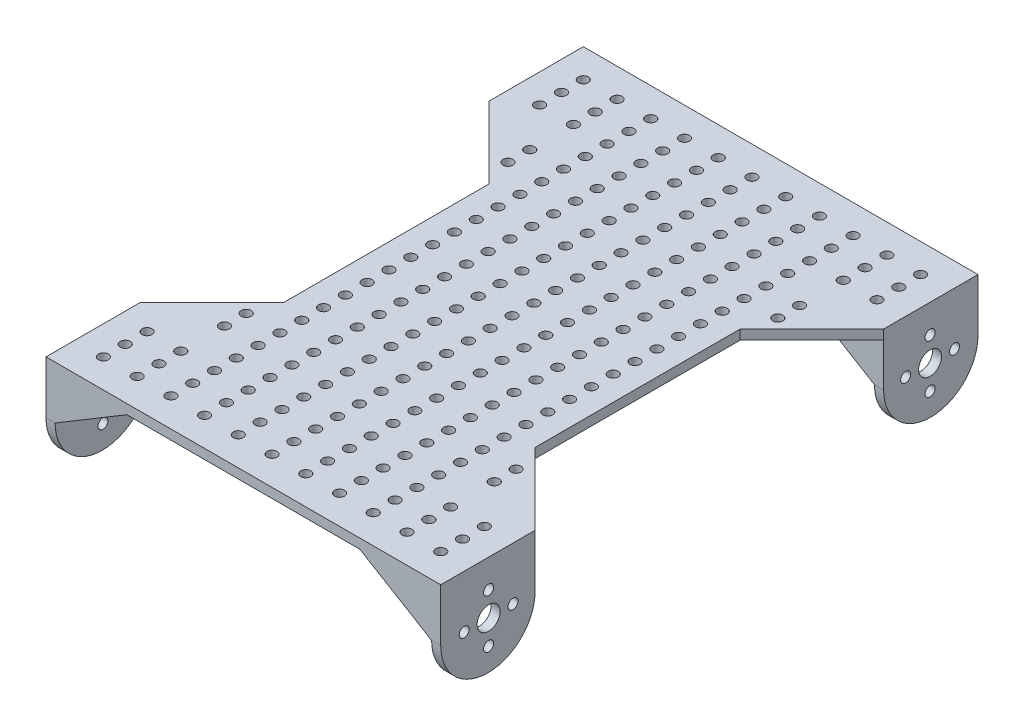
SolidWorks part; units mm, degrees
ref_plane "Alzado" through (0, 0, 0) normal (0, 0, 1) x (1, 0, 0)
ref_plane "Planta" through (0, 0, 0) normal (0, 1, 0) x (1, 0, 0)
ref_plane "Vista lateral" through (0, 0, 0) normal (1, 0, 0) x (0, 0, -1)
sketch "Croquis1" plane through (0, 0, 0) normal (1, 0, 0) x (0, 0, -1)
  point P0 (0, 0)
  line B0 (-60.7, 0) -> (60.7, 0)
  line B1 (-93.6, 0) -> (-93.6, 3.3682)
  line B2 (-93.6, 3.3682) -> (93.6, 3.3682)
  line B3 (-93.6, 0) -> (-93.6, -15)
  line B4 (-60.7, -15) -> (-63.7, -15) construction
  line B5 (-93.6, 0) -> (-60.7, 0) construction
  line B6 (-60.7, -15) -> (-60.7, 0)
  line B7 (0, 3.3682) -> (0, 0) construction
  line B8 (93.6, 0) -> (60.7, 0) construction
  line B9 (60.7, -15) -> (63.7, -15) construction
  line B10 (60.7, -15) -> (60.7, 0)
  line B11 (93.6, 0) -> (93.6, -15)
  line B12 (93.6, 0) -> (93.6, 3.3682)
  line B13 (93.6, 0) -> (60.7, 0) construction
  arc B14 (-93.6, -15) -> (-60.7, -15) centre (-77.15, -15) ccw
  circle B15 centre (-76.9, -15) radius 13.2
  circle B16 centre (76.9, -15) radius 13.2
  arc B17 (93.6, -15) -> (60.7, -15) centre (77.15, -15) cw
  circle B18 centre (-76.9, -23.5) radius 1.75
  circle B19 centre (-85.4, -15) radius 1.75
  circle B20 centre (-68.4, -15) radius 1.75
  circle B21 centre (-76.9, -6.5) radius 1.75
  circle B22 centre (76.9, -6.5) radius 1.75
  circle B23 centre (68.4, -15) radius 1.75
  circle B24 centre (85.4, -15) radius 1.75
  circle B25 centre (76.9, -23.5) radius 1.75
  circle B26 centre (-76.9, -15) radius 4
  circle B27 centre (76.9, -15) radius 4
sketch_block_instance "Bloque1-1"
sketch_block "Bloque1"
extrude "Saliente-Extruir1" add sketch "Croquis1" along normal blind 3.175 contours B17 B11 B12 B2 B1 B3 B14 B6 B0 B10 B15 B16 | B15 B26 B21 B20 B19 B18 | B16 B25 B23 B22 B24 B27 region at (0, -7.5, 62.6041) region at (0, -15, 89.7266) region at (0, -15, -64.0734)
sketch "Croquis3" plane through (3.175, 0, 0) normal (1, 0, 0) x (0, 0, -1)
  line L0 (-93.6, 3.3682) -> (-93.6, 0)
  line L1 (-93.6, -15) -> (-93.6, 3.3682) construction
  line L2 (-93.6, 0) -> (93.6, 0)
  line L3 (93.6, 3.3682) -> (93.6, -15) construction
  line L4 (93.6, 0) -> (93.6, 3.3682)
  line L5 (93.6, 3.3682) -> (-93.6, 3.3682)
extrude "Saliente-Extruir2" add sketch "Croquis3" along normal blind 131.175 and the other way blind 3.175
sketch "Croquis4" plane through (134.35, 0, 0) normal (1, 0, 0) x (0, 0, -1)
  line L0 (93.6, 0) -> (60.7, 0) construction
  line L1 (60.7, 0) -> (60.7, -15) construction
  line L2 (93.6, -15) -> (93.6, 0) construction
  line L3 (-60.7, 0) -> (-93.6, 0) construction
  line L4 (93.6, 3.3682) -> (-93.6, 3.3682)
  line L5 (-93.6, 3.3682) -> (-93.6, 0)
  line L6 (-93.6, 0) -> (93.6, 0)
  line L7 (93.6, 0) -> (93.6, 3.3682)
  line L8 (93.6, 3.3682) -> (-93.6, 3.3682)
  line L9 (-93.6, 3.3682) -> (-93.6, 0)
  line L10 (-93.6, 0) -> (93.6, 0)
  line L11 (93.6, 0) -> (93.6, 3.3682)
  line L12 (-93.6, 0) -> (-93.6, -15) construction
  line L13 (-60.7, -15) -> (-60.7, 0) construction
  line L14 (93.6, 0) -> (60.7, 0)
  line L15 (60.7, 0) -> (60.7, -15)
  line L16 (93.6, -15) -> (93.6, 0)
  line L17 (-60.7, 0) -> (-93.6, 0)
  line L18 (-93.6, 0) -> (-93.6, -15)
  line L19 (-60.7, -15) -> (-60.7, 0)
  arc A0 (60.7, -15) -> (93.6, -15) centre (77.15, -15) ccw construction
  circle A1 centre (76.9, -15) radius 4
  circle A2 centre (76.9, -15) radius 4
  circle A3 centre (85.4, -15) radius 1.75
  circle A4 centre (85.4, -15) radius 1.75
  circle A5 centre (76.9, -6.5) radius 1.75
  circle A6 centre (76.9, -6.5) radius 1.75
  circle A7 centre (68.4, -15) radius 1.75
  circle A8 centre (68.4, -15) radius 1.75
  circle A9 centre (76.9, -23.5) radius 1.75
  circle A10 centre (76.9, -23.5) radius 1.75
  circle A11 centre (-76.9, -15) radius 4
  circle A12 centre (-76.9, -15) radius 4
  circle A13 centre (-76.9, -6.5) radius 1.75
  circle A14 centre (-76.9, -6.5) radius 1.75
  circle A15 centre (-68.4, -15) radius 1.75
  circle A16 centre (-68.4, -15) radius 1.75
  circle A17 centre (-85.4, -15) radius 1.75
  circle A18 centre (-85.4, -15) radius 1.75
  circle A19 centre (-76.9, -23.5) radius 1.75
  circle A20 centre (-76.9, -23.5) radius 1.75
  arc A21 (-93.6, -15) -> (-60.7, -15) centre (-77.15, -15) ccw construction
  arc A22 (60.7, -15) -> (93.6, -15) centre (77.15, -15) ccw
  arc A23 (-93.6, -15) -> (-60.7, -15) centre (-77.15, -15) ccw
  line M16 (93.6, 3.3682) -> (-93.6, 3.3682)
  line M17 (-93.6, 3.3682) -> (-93.6, 0)
  line M18 (-93.6, 0) -> (93.6, 0)
  line M19 (93.6, 0) -> (93.6, 3.3682)
  dimension "D1" = 0
  dimension "D2" = 0
  dimension "D3" = 0
  dimension "D4" = 0
  dimension "D5" = 0
  dimension "D6" = 0
  dimension "D7" = 0
  dimension "D8" = 0
  dimension "D9" = 0
  dimension "D10" = 0
  dimension "D11" = 0
extrude "Saliente-Extruir3" add sketch "Croquis4" along normal blind 3.175 contours L18 A23 L19 A12 A14 A16 A18 A20 M18 | L10 M19 M16 M17 M18 | L15 A22 L16 L10 A2 A4 A6 A8 A10 region at (134.35, 1.6841, 0) region at (134.35, -7.5, -93.1449) region at (134.35, -0.4551, 77.15)
sketch "Croquis5" plane through (0, 3.3682, 0) normal (0, 1, 0) x (1, 0, 0)
  line L0 (0, 60.7) -> (25, 35.7)
  line L1 (0, -93.6) -> (0, 93.6) construction
  line L2 (25, 35.7) -> (25, -35.7)
  line L3 (25, -35.7) -> (0, -60.7)
  line L4 (0, -60.7) -> (0, 60.7)
  line L5 (68.7625, 93.6) -> (68.7625, -93.6) construction
  line L6 (137.525, 93.6) -> (0, 93.6) construction
  line L7 (137.525, -93.6) -> (0, -93.6) construction
  line L8 (137.525, 60.7) -> (112.525, 35.7)
  line L9 (137.525, -60.7) -> (137.525, 60.7)
  line L10 (112.525, -35.7) -> (137.525, -60.7)
  line L11 (112.525, 35.7) -> (112.525, -35.7)
  point P12 (27.0441, -39.4213)
  point P15 (-120.5667, 86.0572)
  dimension "D1" = 32.9
  dimension "D2" = 32.9
  dimension "D3" = 25
  dimension "D4" = 25
  dimension "D5" = 25
extrude "Cortar-Extruir1" cut sketch "Croquis5" against normal through all
sketch "Croquis8" plane through (0, 0, 93.6) normal (0, 0, 1) x (1, 0, 0)
  line L0 (3.175, -15) -> (28.175, 0)
  line L1 (3.175, 0) -> (134.35, 0) construction
  line L2 (28.175, 0) -> (3.175, 0)
  line L3 (3.175, 0) -> (3.175, -15)
  line L4 (68.7625, 0) -> (68.7625, 3.3682) construction
  line L5 (137.525, 3.3682) -> (0, 3.3682) construction
  line L6 (134.35, 0) -> (134.35, -15)
  line L7 (109.35, 0) -> (134.35, 0)
  line L8 (134.35, -15) -> (109.35, 0)
  dimension "D1" = 25
extrude "Saliente-Extruir4" add sketch "Croquis8" against normal up to surface (187.2 mm away) up to face at (68.7625, -6.658, -93.6)
ref_plane "Plano1" through (68.7625, 0, 0) normal (1, 0, 0) x (0, 0, -1)
sketch "Croquis9" plane through (68.7625, 0, 0) normal (1, 0, 0) x (0, 0, -1)
  line L0 (-63.7, -15) -> (-63.7, 0)
  line L1 (-72.9, -15) -> (-80.9, -15) construction
  line L2 (-63.7, 0) -> (-90.6, 0)
  line L3 (-90.6, 0) -> (-90.6, -15)
  line L4 (-90.6, -15) -> (-63.7, -15)
  line L5 (-93.6, 3.3682) -> (-93.6, -15) construction
  line L6 (-60.7, -15) -> (-60.7, 0) construction
  line L7 (57.525, 0) -> (-57.525, 0) construction
  line L8 (60.7, 0) -> (-60.7, 0)
  line L9 (0, 0) -> (0, -15)
  line L10 (60.7, -15) -> (-60.7, -15)
  line L11 (-60.7, 0) -> (-60.7, -15)
  line L12 (90.6, -15) -> (63.7, -15)
  line L13 (90.6, 0) -> (90.6, -15)
  line L14 (63.7, 0) -> (90.6, 0)
  line L15 (63.7, -15) -> (63.7, 0)
  line L16 (60.7, 0) -> (60.7, -15)
  dimension "D1" = 3
  dimension "D2" = 3
extrude "Cortar-Extruir2" cut sketch "Croquis9" along normal up to surface (65.5875 mm away) and the other way up to surface (65.5875 mm away) contours L16 L10 L11 L8 | L13 L12 L15 L14 | L4 L0 L2 L3 up to face at (134.35, -23.5, -78.65) other way up to face at (3.175, -17.9938, -76.9625)
sketch "Croquis10" plane through (0, 3.3682, 0) normal (0, 1, 0) x (1, 0, 0)
  line L0 (0, 60.7) -> (0, 93.6) construction
  line L1 (137.525, 93.6) -> (0, 93.6) construction
  line L2 (137.525, 93.6) -> (137.525, 60.7) construction
  line L3 (10, 83.6) -> (127.525, 83.6) construction
  line L4 (0, -93.6) -> (0, -60.7) construction
  line L5 (137.525, -93.6) -> (0, -93.6) construction
  line L6 (10, 76) -> (127.525, 76) construction
  line L7 (10, 68.4) -> (127.525, 68.4) construction
  line L8 (10, 60.8) -> (127.525, 60.8) construction
  line L9 (10, 53.2) -> (127.525, 53.2) construction
  line L10 (10, 45.6) -> (127.525, 45.6) construction
  line L11 (10, 38) -> (127.525, 38) construction
  line L12 (10, 30.4) -> (127.525, 30.4) construction
  line L13 (10, 22.8) -> (127.525, 22.8) construction
  line L14 (10, 15.2) -> (127.525, 15.2) construction
  line L15 (10, 7.6) -> (127.525, 7.6) construction
  line L16 (10, 0) -> (127.525, 0) construction
  line L17 (10, -7.6) -> (127.525, -7.6) construction
  line L18 (10, -15.2) -> (127.525, -15.2) construction
  line L19 (10, -22.8) -> (127.525, -22.8) construction
  line L20 (10, -30.4) -> (127.525, -30.4) construction
  line L21 (10, -38) -> (127.525, -38) construction
  line L22 (10, -45.6) -> (127.525, -45.6) construction
  line L23 (10, -53.2) -> (127.525, -53.2) construction
  line L24 (10, -60.8) -> (127.525, -60.8) construction
  line L25 (10, -68.4) -> (127.525, -68.4) construction
  line L26 (10, -76) -> (127.525, -76) construction
  line L27 (10, -83.6) -> (127.525, -83.6) construction
  circle A0 centre (10, 83.6) radius 1.75
  circle A1 centre (127.525, 83.6) radius 1.75
  circle A5 centre (21.753, 83.6) radius 1.75
  circle A6 centre (33.506, 83.6) radius 1.75
  circle A7 centre (45.259, 83.6) radius 1.75
  circle A8 centre (57.012, 83.6) radius 1.75
  circle A9 centre (68.765, 83.6) radius 1.75
  circle A10 centre (80.518, 83.6) radius 1.75
  circle A11 centre (92.271, 83.6) radius 1.75
  circle A12 centre (104.024, 83.6) radius 1.75
  circle A13 centre (115.777, 83.6) radius 1.75
  circle A14 centre (127.53, 83.6) radius 1.75
  circle A15 centre (10, -83.6) radius 1.75
  circle A16 centre (10, 76) radius 1.75
  circle A17 centre (127.525, 76) radius 1.75
  circle A18 centre (21.753, 76) radius 1.75
  circle A19 centre (33.506, 76) radius 1.75
  circle A20 centre (45.259, 76) radius 1.75
  circle A21 centre (57.012, 76) radius 1.75
  circle A22 centre (68.765, 76) radius 1.75
  circle A23 centre (80.518, 76) radius 1.75
  circle A24 centre (92.271, 76) radius 1.75
  circle A25 centre (104.024, 76) radius 1.75
  circle A26 centre (115.777, 76) radius 1.75
  circle A27 centre (127.53, 76) radius 1.75
  circle A28 centre (10, 68.4) radius 1.75
  circle A29 centre (127.525, 68.4) radius 1.75
  circle A30 centre (21.753, 68.4) radius 1.75
  circle A31 centre (33.506, 68.4) radius 1.75
  circle A32 centre (45.259, 68.4) radius 1.75
  circle A33 centre (57.012, 68.4) radius 1.75
  circle A34 centre (68.765, 68.4) radius 1.75
  circle A35 centre (80.518, 68.4) radius 1.75
  circle A36 centre (92.271, 68.4) radius 1.75
  circle A37 centre (104.024, 68.4) radius 1.75
  circle A38 centre (115.777, 68.4) radius 1.75
  circle A39 centre (127.53, 68.4) radius 1.75
  circle A40 centre (10, 60.8) radius 1.75 construction
  circle A41 centre (127.525, 60.8) radius 1.75 construction
  circle A42 centre (21.753, 60.8) radius 1.75 construction
  circle A43 centre (33.506, 60.8) radius 1.75
  circle A44 centre (45.259, 60.8) radius 1.75
  circle A45 centre (57.012, 60.8) radius 1.75
  circle A46 centre (68.765, 60.8) radius 1.75
  circle A47 centre (80.518, 60.8) radius 1.75
  circle A48 centre (92.271, 60.8) radius 1.75
  circle A49 centre (104.024, 60.8) radius 1.75
  circle A50 centre (115.777, 60.8) radius 1.75 construction
  circle A51 centre (127.53, 60.8) radius 1.75 construction
  circle A52 centre (10, 53.2) radius 1.75 construction
  circle A53 centre (127.525, 53.2) radius 1.75 construction
  circle A54 centre (21.753, 53.2) radius 1.75
  circle A55 centre (33.506, 53.2) radius 1.75
  circle A56 centre (45.259, 53.2) radius 1.75
  circle A57 centre (57.012, 53.2) radius 1.75
  circle A58 centre (68.765, 53.2) radius 1.75
  circle A59 centre (80.518, 53.2) radius 1.75
  circle A60 centre (92.271, 53.2) radius 1.75
  circle A61 centre (104.024, 53.2) radius 1.75
  circle A62 centre (115.777, 53.2) radius 1.75
  circle A63 centre (127.53, 53.2) radius 1.75 construction
  circle A64 centre (10, 45.6) radius 1.75
  circle A65 centre (127.525, 45.6) radius 1.75
  circle A66 centre (21.753, 45.6) radius 1.75
  circle A67 centre (33.506, 45.6) radius 1.75
  circle A68 centre (45.259, 45.6) radius 1.75
  circle A69 centre (57.012, 45.6) radius 1.75
  circle A70 centre (68.765, 45.6) radius 1.75
  circle A71 centre (80.518, 45.6) radius 1.75
  circle A72 centre (92.271, 45.6) radius 1.75
  circle A73 centre (104.024, 45.6) radius 1.75
  circle A74 centre (115.777, 45.6) radius 1.75
  circle A75 centre (127.53, 45.6) radius 1.75
  circle A76 centre (10, 38) radius 1.75
  circle A77 centre (127.525, 38) radius 1.75
  circle A78 centre (21.753, 38) radius 1.75 construction
  circle A79 centre (33.506, 38) radius 1.75
  circle A80 centre (45.259, 38) radius 1.75
  circle A81 centre (57.012, 38) radius 1.75
  circle A82 centre (68.765, 38) radius 1.75
  circle A83 centre (80.518, 38) radius 1.75
  circle A84 centre (92.271, 38) radius 1.75
  circle A85 centre (104.024, 38) radius 1.75
  circle A86 centre (115.777, 38) radius 1.75 construction
  circle A87 centre (127.53, 38) radius 1.75
  circle A88 centre (10, 30.4) radius 1.75
  circle A89 centre (127.525, 30.4) radius 1.75
  circle A90 centre (21.753, 30.4) radius 1.75
  circle A91 centre (33.506, 30.4) radius 1.75
  circle A92 centre (45.259, 30.4) radius 1.75
  circle A93 centre (57.012, 30.4) radius 1.75
  circle A94 centre (68.765, 30.4) radius 1.75
  circle A95 centre (80.518, 30.4) radius 1.75
  circle A96 centre (92.271, 30.4) radius 1.75
  circle A97 centre (104.024, 30.4) radius 1.75
  circle A98 centre (115.777, 30.4) radius 1.75
  circle A99 centre (127.53, 30.4) radius 1.75
  circle A100 centre (10, 22.8) radius 1.75
  circle A101 centre (127.525, 22.8) radius 1.75
  circle A102 centre (21.753, 22.8) radius 1.75
  circle A103 centre (33.506, 22.8) radius 1.75
  circle A104 centre (45.259, 22.8) radius 1.75
  circle A105 centre (57.012, 22.8) radius 1.75
  circle A106 centre (68.765, 22.8) radius 1.75
  circle A107 centre (80.518, 22.8) radius 1.75
  circle A108 centre (92.271, 22.8) radius 1.75
  circle A109 centre (104.024, 22.8) radius 1.75
  circle A110 centre (115.777, 22.8) radius 1.75
  circle A111 centre (127.53, 22.8) radius 1.75
  circle A112 centre (10, 15.2) radius 1.75
  circle A113 centre (127.525, 15.2) radius 1.75
  circle A114 centre (21.753, 15.2) radius 1.75
  circle A115 centre (33.506, 15.2) radius 1.75
  circle A116 centre (45.259, 15.2) radius 1.75
  circle A117 centre (57.012, 15.2) radius 1.75
  circle A118 centre (68.765, 15.2) radius 1.75
  circle A119 centre (80.518, 15.2) radius 1.75
  circle A120 centre (92.271, 15.2) radius 1.75
  circle A121 centre (104.024, 15.2) radius 1.75
  circle A122 centre (115.777, 15.2) radius 1.75
  circle A123 centre (127.53, 15.2) radius 1.75
  circle A124 centre (10, 7.6) radius 1.75
  circle A125 centre (127.525, 7.6) radius 1.75
  circle A126 centre (21.753, 7.6) radius 1.75
  circle A127 centre (33.506, 7.6) radius 1.75
  circle A128 centre (45.259, 7.6) radius 1.75
  circle A129 centre (57.012, 7.6) radius 1.75
  circle A130 centre (68.765, 7.6) radius 1.75
  circle A131 centre (80.518, 7.6) radius 1.75
  circle A132 centre (92.271, 7.6) radius 1.75
  circle A133 centre (104.024, 7.6) radius 1.75
  circle A134 centre (115.777, 7.6) radius 1.75
  circle A135 centre (127.53, 7.6) radius 1.75
  circle A136 centre (10, 0) radius 1.75
  circle A137 centre (127.525, 0) radius 1.75
  circle A138 centre (21.753, 0) radius 1.75
  circle A139 centre (33.506, 0) radius 1.75
  circle A140 centre (45.259, 0) radius 1.75
  circle A141 centre (57.012, 0) radius 1.75
  circle A142 centre (68.765, 0) radius 1.75
  circle A143 centre (80.518, 0) radius 1.75
  circle A144 centre (92.271, 0) radius 1.75
  circle A145 centre (104.024, 0) radius 1.75
  circle A146 centre (115.777, 0) radius 1.75
  circle A147 centre (127.53, 0) radius 1.75
  circle A148 centre (10, -7.6) radius 1.75
  circle A149 centre (127.525, -7.6) radius 1.75
  circle A150 centre (21.753, -7.6) radius 1.75
  circle A151 centre (33.506, -7.6) radius 1.75
  circle A152 centre (45.259, -7.6) radius 1.75
  circle A153 centre (57.012, -7.6) radius 1.75
  circle A154 centre (68.765, -7.6) radius 1.75
  circle A155 centre (80.518, -7.6) radius 1.75
  circle A156 centre (92.271, -7.6) radius 1.75
  circle A157 centre (104.024, -7.6) radius 1.75
  circle A158 centre (115.777, -7.6) radius 1.75
  circle A159 centre (127.53, -7.6) radius 1.75
  circle A160 centre (10, -15.2) radius 1.75
  circle A161 centre (127.525, -15.2) radius 1.75
  circle A162 centre (21.753, -15.2) radius 1.75
  circle A163 centre (33.506, -15.2) radius 1.75
  circle A164 centre (45.259, -15.2) radius 1.75
  circle A165 centre (57.012, -15.2) radius 1.75
  circle A166 centre (68.765, -15.2) radius 1.75
  circle A167 centre (80.518, -15.2) radius 1.75
  circle A168 centre (92.271, -15.2) radius 1.75
  circle A169 centre (104.024, -15.2) radius 1.75
  circle A170 centre (115.777, -15.2) radius 1.75
  circle A171 centre (127.53, -15.2) radius 1.75
  circle A172 centre (10, -22.8) radius 1.75
  circle A173 centre (127.525, -22.8) radius 1.75
  circle A174 centre (21.753, -22.8) radius 1.75
  circle A175 centre (33.506, -22.8) radius 1.75
  circle A176 centre (45.259, -22.8) radius 1.75
  circle A177 centre (57.012, -22.8) radius 1.75
  circle A178 centre (68.765, -22.8) radius 1.75
  circle A179 centre (80.518, -22.8) radius 1.75
  circle A180 centre (92.271, -22.8) radius 1.75
  circle A181 centre (104.024, -22.8) radius 1.75
  circle A182 centre (115.777, -22.8) radius 1.75
  circle A183 centre (127.53, -22.8) radius 1.75
  circle A184 centre (10, -30.4) radius 1.75
  circle A185 centre (127.525, -30.4) radius 1.75
  circle A186 centre (21.753, -30.4) radius 1.75
  circle A187 centre (33.506, -30.4) radius 1.75
  circle A188 centre (45.259, -30.4) radius 1.75
  circle A189 centre (57.012, -30.4) radius 1.75
  circle A190 centre (68.765, -30.4) radius 1.75
  circle A191 centre (80.518, -30.4) radius 1.75
  circle A192 centre (92.271, -30.4) radius 1.75
  circle A193 centre (104.024, -30.4) radius 1.75
  circle A194 centre (115.777, -30.4) radius 1.75
  circle A195 centre (127.53, -30.4) radius 1.75
  circle A196 centre (10, -38) radius 1.75
  circle A197 centre (127.525, -38) radius 1.75
  circle A198 centre (21.753, -38) radius 1.75 construction
  circle A199 centre (33.506, -38) radius 1.75
  circle A200 centre (45.259, -38) radius 1.75
  circle A201 centre (57.012, -38) radius 1.75
  circle A202 centre (68.765, -38) radius 1.75
  circle A203 centre (80.518, -38) radius 1.75
  circle A204 centre (92.271, -38) radius 1.75
  circle A205 centre (104.024, -38) radius 1.75
  circle A206 centre (115.777, -38) radius 1.75 construction
  circle A207 centre (127.53, -38) radius 1.75
  circle A208 centre (10, -45.6) radius 1.75
  circle A209 centre (127.525, -45.6) radius 1.75
  circle A210 centre (21.753, -45.6) radius 1.75
  circle A211 centre (33.506, -45.6) radius 1.75
  circle A212 centre (45.259, -45.6) radius 1.75
  circle A213 centre (57.012, -45.6) radius 1.75
  circle A214 centre (68.765, -45.6) radius 1.75
  circle A215 centre (80.518, -45.6) radius 1.75
  circle A216 centre (92.271, -45.6) radius 1.75
  circle A217 centre (104.024, -45.6) radius 1.75
  circle A218 centre (115.777, -45.6) radius 1.75
  circle A219 centre (127.53, -45.6) radius 1.75
  circle A220 centre (10, -53.2) radius 1.75 construction
  circle A221 centre (127.525, -53.2) radius 1.75 construction
  circle A222 centre (21.753, -53.2) radius 1.75
  circle A223 centre (33.506, -53.2) radius 1.75
  circle A224 centre (45.259, -53.2) radius 1.75
  circle A225 centre (57.012, -53.2) radius 1.75
  circle A226 centre (68.765, -53.2) radius 1.75
  circle A227 centre (80.518, -53.2) radius 1.75
  circle A228 centre (92.271, -53.2) radius 1.75
  circle A229 centre (104.024, -53.2) radius 1.75
  circle A230 centre (115.777, -53.2) radius 1.75
  circle A231 centre (127.53, -53.2) radius 1.75 construction
  circle A232 centre (10, -60.8) radius 1.75 construction
  circle A233 centre (127.525, -60.8) radius 1.75 construction
  circle A234 centre (21.753, -60.8) radius 1.75 construction
  circle A235 centre (33.506, -60.8) radius 1.75
  circle A236 centre (45.259, -60.8) radius 1.75
  circle A237 centre (57.012, -60.8) radius 1.75
  circle A238 centre (68.765, -60.8) radius 1.75
  circle A239 centre (80.518, -60.8) radius 1.75
  circle A240 centre (92.271, -60.8) radius 1.75
  circle A241 centre (104.024, -60.8) radius 1.75
  circle A242 centre (115.777, -60.8) radius 1.75 construction
  circle A243 centre (127.53, -60.8) radius 1.75 construction
  circle A244 centre (10, -68.4) radius 1.75
  circle A245 centre (127.525, -68.4) radius 1.75
  circle A246 centre (21.753, -68.4) radius 1.75
  circle A247 centre (33.506, -68.4) radius 1.75
  circle A248 centre (45.259, -68.4) radius 1.75
  circle A249 centre (57.012, -68.4) radius 1.75
  circle A250 centre (68.765, -68.4) radius 1.75
  circle A251 centre (80.518, -68.4) radius 1.75
  circle A252 centre (92.271, -68.4) radius 1.75
  circle A253 centre (104.024, -68.4) radius 1.75
  circle A254 centre (115.777, -68.4) radius 1.75
  circle A255 centre (127.53, -68.4) radius 1.75
  circle A256 centre (10, -76) radius 1.75
  circle A257 centre (127.525, -76) radius 1.75
  circle A258 centre (21.753, -76) radius 1.75
  circle A259 centre (33.506, -76) radius 1.75
  circle A260 centre (45.259, -76) radius 1.75
  circle A261 centre (57.012, -76) radius 1.75
  circle A262 centre (68.765, -76) radius 1.75
  circle A263 centre (80.518, -76) radius 1.75
  circle A264 centre (92.271, -76) radius 1.75
  circle A265 centre (104.024, -76) radius 1.75
  circle A266 centre (115.777, -76) radius 1.75
  circle A267 centre (127.53, -76) radius 1.75
  circle A268 centre (10, -83.6) radius 1.75
  circle A269 centre (127.525, -83.6) radius 1.75
  circle A270 centre (21.753, -83.6) radius 1.75
  circle A271 centre (33.506, -83.6) radius 1.75
  circle A272 centre (45.259, -83.6) radius 1.75
  circle A273 centre (57.012, -83.6) radius 1.75
  circle A274 centre (68.765, -83.6) radius 1.75
  circle A275 centre (80.518, -83.6) radius 1.75
  circle A276 centre (92.271, -83.6) radius 1.75
  circle A277 centre (104.024, -83.6) radius 1.75
  circle A278 centre (115.777, -83.6) radius 1.75
  circle A279 centre (127.53, -83.6) radius 1.75
  dimension "D1" = 3.5
  dimension "D8" = 3.5
  dimension "D9" = 10
  dimension "D2" = 10
  dimension "D3" = 10
  dimension "D5" = 10
  dimension "D7" = 11.753
  dimension "D10" = 10
  dimension "D12" = 7.6
  dimension "D4" = 2
  dimension "D6" = 11
  dimension "D11" = 23
extrude "Cortar-Extruir3" cut sketch "Croquis10" against normal through all
